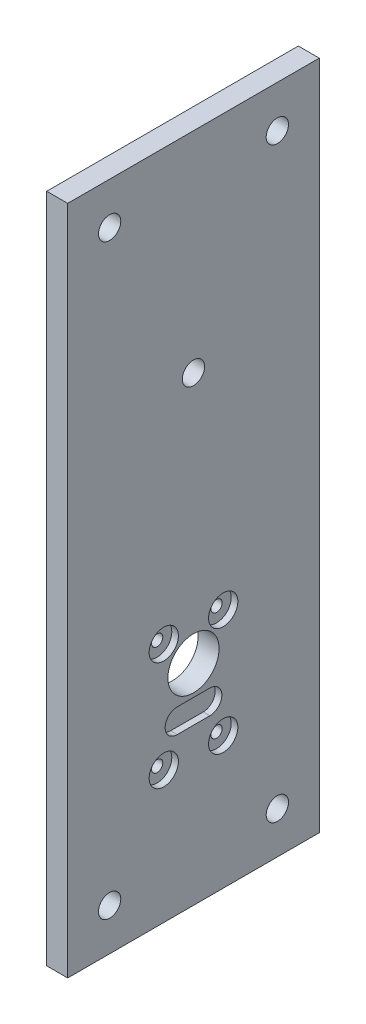
SolidWorks part; units mm, degrees
ref_plane "Front Plane" through (0, 0, 0) normal (0, 0, 1) x (1, 0, 0)
ref_plane "Top Plane" through (0, 0, 0) normal (0, 1, 0) x (1, 0, 0)
ref_plane "Right Plane" through (0, 0, 0) normal (1, 0, 0) x (0, 0, -1)
sketch "Sketch1" plane through (0, 0, 0) normal (1, 0, 0) x (0, 0, -1)
  line L2 (-7.5973, 29.9808) -> (-7.5973, 106.1808) construction
  line L11 (-7.5973, -33.5192) -> (-7.5973, 169.6808) construction
  line L15 (30.5027, -33.5192) -> (30.5027, 169.6808)
  line L16 (30.5027, 169.6808) -> (-45.6973, 169.6808)
  line L17 (-45.6973, 169.6808) -> (-45.6973, -33.5192)
  line L18 (-45.6973, -33.5192) -> (30.5027, -33.5192)
  arc A0 (-7.5973, -4.9442) -> (26.2187, 38.7121) centre (-7.5973, 29.9808) ccw construction
  arc A1 (4.6994, 109.3558) -> (-19.894, 109.3558) centre (-7.5973, 106.1808) ccw construction
  arc A2 (26.2187, 38.7121) -> (-41.4133, 38.7121) centre (-7.5973, 29.9808) ccw construction
  arc A3 (-19.894, 109.3558) -> (4.6994, 109.3558) centre (-7.5973, 106.1808) ccw construction
  circle A4 centre (-7.5973, 106.1808) radius 3.175 construction
  circle A5 centre (-7.5973, 29.9808) radius 7.75
  arc A6 (-41.4133, 38.7121) -> (-7.5973, -4.9442) centre (-7.5973, 29.9808) ccw construction
  circle A18 centre (-7.5973, 29.9808) radius 9.525 construction
  dimension "D1" = 34.925
  dimension "D2" = 25.4
  dimension "D4" = 6.35
  dimension "D5" = 15.5
  dimension "D6" = 76.2
  dimension "D7" = 203.2
  dimension "D3" = 139.7
  dimension "D12" = 63.5
extrude "Boss-Extrude1" add sketch "Sketch1" along normal blind 6.35 contours L17 L18 L15 L16 A4 A5 region at (0, 68.5509, 7.5973)
sketch "Sketch7" plane through (6.35, 0, 0) normal (1, 0, 0) x (0, 0, -1)
  line L0 (-12.5473, 20.3808) -> (-2.6473, 20.3808) construction
  line L1 (-2.6473, 14.3808) -> (-12.5473, 14.3808) construction
  line L2 (-12.5473, 20.3808) -> (-2.6473, 20.3808) construction
  line L3 (-2.6473, 14.3808) -> (-12.5473, 14.3808) construction
  line L4 (-12.5473, 21.0158) -> (-2.6473, 21.0158)
  line L5 (-2.6473, 13.7458) -> (-12.5473, 13.7458)
  circle A0 centre (-7.5973, 29.9808) radius 6.6 construction
  circle A1 centre (1.4027, 39.5202) radius 3.8 construction
  circle A2 centre (-16.5973, 39.5202) radius 3.8 construction
  arc A3 (-12.5473, 20.3808) -> (-12.5473, 14.3808) centre (-12.5473, 17.3808) ccw construction
  arc A4 (-2.6473, 14.3808) -> (-2.6473, 20.3808) centre (-2.6473, 17.3808) ccw construction
  circle A5 centre (1.4027, 6.5202) radius 3.8 construction
  circle A6 centre (-16.5973, 6.5202) radius 3.8 construction
  circle A7 centre (-7.5973, 29.9808) radius 6.6 construction
  circle A8 centre (1.4027, 39.5202) radius 3.8 construction
  circle A9 centre (-16.5973, 39.5202) radius 3.8 construction
  arc A10 (-12.5473, 20.3808) -> (-12.5473, 14.3808) centre (-12.5473, 17.3808) ccw construction
  arc A11 (-2.6473, 14.3808) -> (-2.6473, 20.3808) centre (-2.6473, 17.3808) ccw construction
  circle A12 centre (1.4027, 6.5202) radius 3.8 construction
  circle A13 centre (-16.5973, 6.5202) radius 3.8 construction
  arc A14 (-2.6473, 13.7458) -> (-2.6473, 21.0158) centre (-2.6473, 17.3808) ccw
  arc A15 (-12.5473, 21.0158) -> (-12.5473, 13.7458) centre (-12.5473, 17.3808) ccw
  circle A16 centre (-7.5973, 29.9808) radius 7.235
  circle A17 centre (1.4027, 39.5202) radius 4.435
  circle A18 centre (-16.5973, 39.5202) radius 4.435
  circle A19 centre (1.4027, 6.5202) radius 4.435
  circle A20 centre (-16.5973, 6.5202) radius 4.435
  dimension "D1" = 0.635
extrude "Cut-Extrude2" cut sketch "Sketch7" against normal blind 2
hole_wizard "M3 Clearance Hole2" positions "Sketch8" profile "Sketch9" hole size "M3" standard "ANSI Metric" end condition through all
sketch "Sketch8" plane through (6.35, 0, 0) normal (1, 0, 0) x (0, 0, -1)
  point P0 (1.4027, 6.5202)
  point P3 (-16.5973, 6.5202)
  point P6 (-16.5973, 39.5202)
  point P9 (1.4027, 39.5202)
sketch "Sketch9" plane through (6.35, 6.5202, -1.4027) normal (0, 1, 0) x (0, 0, -1)
  line L0 (0, 0) -> (0, 6.35)
  line L1 (0, 6.35) -> (1.7, 6.35)
  line L2 (1.7, 6.35) -> (1.7, 0)
  line L5 (1.7, 0) -> (0, 0)
  line L11 (0, -6.35) -> (0, 107.95) construction
  dimension "Thru Hole Dia." = 3.4
  dimension "Thru Hole Depth" = 6.35
hole_wizard "1/4 Clearance Hole1" positions "Sketch10" profile "Sketch11" hole size "1/4" standard "ANSI Inch" end condition through all
sketch "Sketch10" plane through (6.35, 0, 0) normal (1, 0, 0) x (0, 0, -1)
  line L1 (-45.6973, -33.5192) -> (30.5027, -33.5192) construction
  line L2 (-32.9973, 156.9808) -> (17.8027, 156.9808) construction
  line L4 (-7.5973, 169.6808) -> (-7.5973, -33.5192) construction
  line L5 (30.5027, 169.6808) -> (-45.6973, 169.6808) construction
  line L6 (-32.9973, -20.8192) -> (17.8027, -20.8192) construction
  line L8 (-45.6973, 169.6808) -> (-45.6973, -33.5192) construction
  point P0 (-32.9973, -20.8192)
  point P3 (17.8027, -20.8192)
  point P6 (-7.5973, 106.1808)
  point P9 (-32.9973, 156.9808)
  point P11 (17.8027, 156.9808)
  point P25 (-7.5973, 156.9808)
  dimension "D1" = 190.5
  dimension "D2" = 12.7
  dimension "D3" = 139.7
  dimension "D5" = 12.7
  dimension "D6" = 50.8
sketch "Sketch11" plane through (6.35, -20.8192, 32.9973) normal (0, 1, 0) x (0, 0, -1)
  line L0 (0, 0) -> (0, 6.35)
  line L1 (0, 6.35) -> (3.3782, 6.35)
  line L2 (3.3782, 6.35) -> (3.3782, 0)
  line L5 (3.3782, 0) -> (0, 0)
  line L11 (0, -6.35) -> (0, 107.95) construction
  dimension "Thru Hole Dia." = 6.7564
  dimension "Thru Hole Depth" = 6.35
